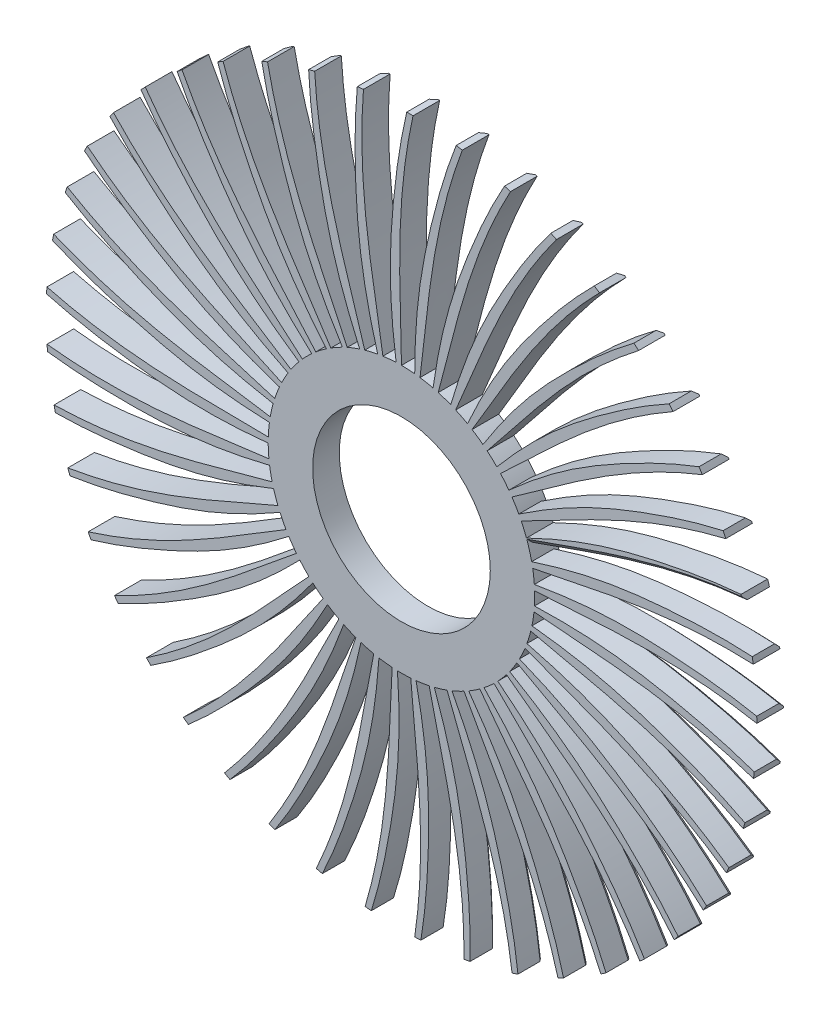
SolidWorks part; units mm, degrees
ref_plane "Front Plane" through (0, 0, 0) normal (0, 0, 1) x (1, 0, 0)
ref_plane "Top Plane" through (0, 0, 0) normal (0, 1, 0) x (1, 0, 0)
ref_plane "Right Plane" through (0, 0, 0) normal (1, 0, 0) x (0, 0, -1)
sketch "Sketch2" plane through (0, 0, 0) normal (0, 0, 1) x (1, 0, 0)
  arc A0 (13, 399.7887) -> (6, 399.955) centre (0, 0) ccw
  arc A1 (-6, 149.88) -> (-20.876, 148.5402) centre (0, 0) ccw
  arc A2 (68.5133, 394.0887) -> (61.6046, 395.2276) centre (0, 0) ccw
  arc A3 (122.6931, 380.7183) -> (116.0101, 382.8076) centre (0, 0) ccw
  arc A4 (174.4848, 359.9376) -> (168.1576, 362.9367) centre (0, 0) ccw
  arc A5 (222.8804, 332.1511) -> (217.0321, 336.0016) centre (0, 0) ccw
  arc A6 (266.9378, 297.8997) -> (261.6824, 302.5266) centre (0, 0) ccw
  arc A7 (305.7996, 257.85) -> (301.2393, 263.1633) centre (0, 0) ccw
  arc A8 (338.7094, 212.7815) -> (334.9329, 218.6778) centre (0, 0) ccw
  arc A9 (365.0265, 163.5715) -> (362.1074, 169.936) centre (0, 0) ccw
  arc A10 (384.2389, 111.1778) -> (382.2339, 117.8866) centre (0, 0) ccw
  arc A11 (395.9724, 56.6201) -> (394.9207, 63.5426) centre (0, 0) ccw
  arc A12 (399.9988, 0.9603) -> (399.9208, 7.9619) centre (0, 0) ccw
  arc A13 (396.2397, -54.7181) -> (397.1368, -47.7738) centre (0, 0) ccw
  arc A14 (384.7683, -109.3315) -> (386.6231, -102.5796) centre (0, 0) ccw
  arc A15 (365.8077, -161.8169) -> (368.5842, -155.3889) centre (0, 0) ccw
  arc A16 (339.7272, -211.1527) -> (343.3712, -205.1737) centre (0, 0) ccw
  arc A17 (307.0342, -256.3786) -> (311.4749, -250.9649) centre (0, 0) ccw
  arc A18 (268.3651, -296.6145) -> (273.516, -291.8715) centre (0, 0) ccw
  arc A19 (224.4727, -331.0771) -> (230.2335, -327.0971) centre (0, 0) ccw
  arc A20 (176.2111, -359.0956) -> (182.4698, -355.9561) centre (0, 0) ccw
  arc A21 (124.5198, -380.1247) -> (131.1545, -377.8869) centre (0, 0) ccw
  arc A22 (70.4048, -393.7552) -> (77.2864, -392.4625) centre (0, 0) ccw
  arc A23 (14.9195, -399.7217) -> (21.9141, -399.3993) centre (0, 0) ccw
  arc A24 (-40.8562, -397.908) -> (-33.8848, -398.5622) centre (0, 0) ccw
  arc A25 (-95.8367, -388.3495) -> (-89.0242, -389.9676) centre (0, 0) ccw
  arc A26 (-148.9518, -371.2322) -> (-142.4308, -373.7826) centre (0, 0) ccw
  arc A27 (-199.1677, -346.8893) -> (-193.0652, -350.3225) centre (0, 0) ccw
  arc A28 (-245.5071, -315.7946) -> (-239.9418, -320.0437) centre (0, 0) ccw
  arc A29 (-287.068, -278.5534) -> (-282.1481, -283.5356) centre (0, 0) ccw
  arc A30 (-323.0414, -235.8904) -> (-318.8628, -241.5088) centre (0, 0) ccw
  arc A31 (-352.7272, -188.636) -> (-349.3712, -194.7813) centre (0, 0) ccw
  arc A32 (-375.5475, -137.7101) -> (-373.0795, -144.2627) centre (0, 0) ccw
  arc A33 (-391.0582, -84.1038) -> (-389.5262, -90.9361) centre (0, 0) ccw
  arc A34 (-398.9575, -28.8605) -> (-398.3912, -35.8395) centre (0, 0) ccw
  arc A35 (-399.0915, 26.9445) -> (-399.502, 19.9546) centre (0, 0) ccw
  arc A36 (-391.4576, 82.2251) -> (-392.8369, 75.3603) centre (0, 0) ccw
  arc A37 (-376.2044, 135.9052) -> (-378.5257, 129.2992) centre (0, 0) ccw
  arc A38 (-353.6289, 186.9402) -> (-356.8469, 180.7215) centre (0, 0) ccw
  arc A39 (-324.1703, 234.3365) -> (-328.2226, 228.6262) centre (0, 0) ccw
  arc A40 (-288.4022, 277.1717) -> (-293.2097, 272.081) centre (0, 0) ccw
  arc A41 (-247.0206, 314.6121) -> (-252.4899, 310.24) centre (0, 0) ccw
  arc A42 (-200.8311, 345.929) -> (-206.8556, 342.3606) centre (0, 0) ccw
  arc A43 (-150.7326, 370.5127) -> (-157.1951, 367.8175) centre (0, 0) ccw
  arc A44 (-97.7003, 387.8848) -> (-104.475, 386.1152) centre (0, 0) ccw
  arc A45 (-42.7663, 397.7072) -> (-49.7214, 396.8977) centre (0, 0) ccw
  arc A46 (-26.8009, 147.5863) -> (-41.3456, 144.1893) centre (0, 0) ccw
  arc A47 (-47.0801, 142.42) -> (-61.0105, 137.0318) centre (0, 0) ccw
  arc A48 (35.5449, 145.7277) -> (20.876, 148.5402) centre (0, 0) ccw
  arc A49 (14.9176, 149.2564) -> (0, 150) centre (0, 0) ccw
  arc A50 (-66.4429, 134.4817) -> (-79.4879, 127.2072) centre (0, 0) ccw
  arc A51 (-84.5126, 123.9259) -> (-96.4181, 114.9067) centre (0, 0) ccw
  arc A52 (-100.9372, 110.958) -> (-111.4717, 100.3696) centre (0, 0) ccw
  arc A53 (55.4804, 139.3626) -> (41.3456, 144.1893) centre (0, 0) ccw
  arc A54 (74.336, 130.2849) -> (61.0105, 137.0318) centre (0, 0) ccw
  arc A55 (91.7447, 118.6714) -> (79.4879, 127.2072) centre (0, 0) ccw
  arc A56 (-115.3973, 95.8304) -> (-124.3556, 83.8789) centre (0, 0) ccw
  arc A57 (-127.6113, 78.8376) -> (-134.8191, 65.7557) centre (0, 0) ccw
  arc A58 (107.3677, 104.7481) -> (96.4181, 114.9067) centre (0, 0) ccw
  arc A59 (120.901, 88.786) -> (111.4717, 100.3696) centre (0, 0) ccw
  arc A60 (132.081, 71.0958) -> (124.3556, 83.8789) centre (0, 0) ccw
  arc A61 (-137.3414, 60.3103) -> (-142.6585, 46.3525) centre (0, 0) ccw
  arc A62 (140.6902, 52.0218) -> (134.8191, 65.7557) centre (0, 0) ccw
  arc A63 (146.561, 31.9352) -> (142.6585, 46.3525) centre (0, 0) ccw
  arc A64 (-144.3984, 40.6091) -> (-147.7212, 26.0472) centre (0, 0) ccw
  arc A65 (-148.6448, 20.1175) -> (-149.9086, 5.2349) centre (0, 0) ccw
  arc A66 (-149.998, -0.7656) -> (-149.1783, -15.6793) centre (0, 0) ccw
  arc A67 (-148.4317, -21.6339) -> (-145.5444, -36.2883) centre (0, 0) ccw
  arc A68 (-143.9763, -42.081) -> (-139.0776, -56.191) centre (0, 0) ccw
  arc A69 (-136.7186, -61.7091) -> (-129.9038, -75) centre (0, 0) ccw
  arc A70 (-126.7998, -80.1361) -> (-118.2016, -92.3492) centre (0, 0) ccw
  arc A71 (-114.413, -97.0034) -> (-104.1988, -107.901) centre (0, 0) ccw
  arc A72 (-99.7993, -111.9826) -> (-88.1678, -121.3525) centre (0, 0) ccw
  arc A73 (-83.2431, -124.7821) -> (-70.4207, -132.4421) centre (0, 0) ccw
  arc A74 (-65.0667, -135.153) -> (-51.303, -140.9539) centre (0, 0) ccw
  arc A75 (-45.6238, -142.8932) -> (-31.1868, -146.7221) centre (0, 0) ccw
  arc A76 (-25.2929, -147.8522) -> (-10.4635, -149.6346) centre (0, 0) ccw
  arc A77 (-4.4697, -149.9334) -> (10.4635, -149.6346) centre (0, 0) ccw
  arc A78 (16.4405, -149.0963) -> (31.1868, -146.7221) centre (0, 0) ccw
  arc A79 (37.0307, -145.3572) -> (51.303, -140.9539) centre (0, 0) ccw
  arc A80 (56.9001, -138.789) -> (70.4207, -132.4421) centre (0, 0) ccw
  arc A81 (75.6621, -129.5193) -> (88.1678, -121.3525) centre (0, 0) ccw
  arc A82 (108.4314, -103.6467) -> (118.2016, -92.3492) centre (0, 0) ccw
  arc A83 (121.801, -87.5472) -> (129.9038, -75) centre (0, 0) ccw
  arc A84 (132.7998, -69.7438) -> (139.0776, -56.191) centre (0, 0) ccw
  arc A85 (141.2139, -50.5829) -> (145.5444, -36.2883) centre (0, 0) ccw
  arc A86 (146.8794, -30.4375) -> (149.1783, -15.6793) centre (0, 0) ccw
  arc A87 (92.9513, -117.7287) -> (104.1988, -107.901) centre (0, 0) ccw
  arc A88 (149.6861, -9.6996) -> (149.9086, 5.2349) centre (0, 0) ccw
  arc A89 (149.5793, 11.2271) -> (147.7212, 26.0472) centre (0, 0) ccw
  spline S0 degree 3 poles (-6, 149.88) (-14.2223, 209.3858) (-13.846, 280.4019) (-1.5196, 368.6352) (6, 399.955) knots 0 0 0 0 0.599001 1 1 1 1
  spline S1 degree 3 poles (0, 150) (-1.7256, 233.452) (-7.2854, 307.5642) (13, 399.7887) knots 0 0 0 0 1 1 1 1
  spline S2 degree 3 poles (14.9176, 149.2564) (15.0569, 209.3274) (25.3131, 279.6) (49.7993, 365.2591) (61.6046, 395.2276) knots 0 0 0 0 0.599001 1 1 1 1
  spline S3 degree 3 poles (20.876, 148.5402) (30.7814, 231.4203) (35.5902, 305.585) (68.5133, 394.0887) knots 0 0 0 0 1 1 1 1
  spline S4 degree 3 poles (35.5449, 145.7277) (44.0431, 205.1947) (63.9796, 273.3561) (100.1489, 354.7737) (116.0101, 382.8076) knots 0 0 0 0 0.599001 1 1 1 1
  spline S5 degree 3 poles (41.3456, 144.1893) (62.6894, 224.8841) (77.7731, 297.6578) (122.6931, 380.7183) knots 0 0 0 0 1 1 1 1
  spline S6 degree 3 poles (55.4804, 139.3626) (72.1721, 197.0682) (101.4007, 261.7916) (148.5492, 337.3831) (168.1576, 362.9367) knots 0 0 0 0 0.599001 1 1 1 1
  spline S7 degree 3 poles (61.0105, 137.0318) (93.3771, 213.9709) (118.4421, 283.9371) (174.4848, 359.9376) knots 0 0 0 0 1 1 1 1
  spline S8 degree 3 poles (74.336, 130.2849) (98.8963, 185.1059) (136.8482, 245.1316) (194.0581, 313.4256) (217.0321, 336.0016) knots 0 0 0 0 0.599001 1 1 1 1
  spline S9 degree 3 poles (79.4879, 127.2072) (122.2473, 198.893) (156.8059, 264.6899) (222.8804, 332.1511) knots 0 0 0 0 1 1 1 1
  spline S10 degree 3 poles (91.7447, 118.6714) (123.6956, 169.5408) (169.6322, 223.7004) (235.79, 283.3677) (261.6824, 302.5266) knots 0 0 0 0 0.599001 1 1 1 1
  spline S11 degree 3 poles (96.4181, 114.9067) (148.7382, 179.9438) (192.1176, 240.2908) (266.9378, 297.8997) knots 0 0 0 0 1 1 1 1
  spline S12 degree 3 poles (107.3677, 104.7481) (146.0874, 150.6757) (199.1144, 197.9151) (272.9325, 247.7944) (301.2393, 263.1633) knots 0 0 0 0 0.599001 1 1 1 1
  spline S13 degree 3 poles (111.4717, 100.3696) (172.334, 157.4923) (223.6899, 211.2147) (305.7996, 257.85) knots 0 0 0 0 1 1 1 1
  spline S14 degree 3 poles (120.901, 88.786) (165.6356, 128.8779) (224.7211, 168.2776) (304.7626, 207.398) (334.9329, 218.6778) knots 0 0 0 0 0.599001 1 1 1 1
  spline S15 degree 3 poles (124.3556, 83.8789) (192.5756, 131.9753) (250.9084, 178.0276) (338.7094, 212.7815) knots 0 0 0 0 1 1 1 1
  spline S16 degree 3 poles (132.081, 71.0958) (181.96, 104.5716) (245.9538, 135.3648) (330.6609, 162.9649) (362.1074, 169.936) knots 0 0 0 0 0.599001 1 1 1 1
  spline S17 degree 3 poles (134.8191, 65.7557) (209.0689, 103.8896) (273.2432, 141.3753) (365.0265, 163.5715) knots 0 0 0 0 1 1 1 1
  spline S18 degree 3 poles (140.6902, 52.0218) (194.7428, 78.23) (262.3994, 99.8173) (350.1233, 115.3598) (382.2339, 117.8866) knots 0 0 0 0 0.599001 1 1 1 1
  spline S19 degree 3 poles (142.6585, 46.3525) (221.4928, 73.7818) (290.2597, 101.9714) (384.2389, 111.1778) knots 0 0 0 0 1 1 1 1
  spline S20 degree 3 poles (146.561, 31.9352) (203.7351, 50.3657) (273.7376, 62.327) (362.7709, 65.5094) (394.9207, 63.5426) knots 0 0 0 0 0.599001 1 1 1 1
  spline S21 degree 3 poles (147.7212, 26.0472) (229.6057, 42.2379) (301.6266, 60.5827) (395.9724, 56.6201) knots 0 0 0 0 1 1 1 1
  spline S22 degree 3 poles (149.5793, 11.2271) (208.7619, 21.5211) (279.7478, 23.6235) (368.3576, 14.3839) (399.9208, 7.9619) knots 0 0 0 0 0.599001 1 1 1 1
  spline S23 degree 3 poles (149.9086, 5.2349) (233.2496, 9.8719) (307.1226, 18.0148) (399.9988, 0.9603) knots 0 0 0 0 1 1 1 1
  spline S24 degree 3 poles (149.6861, -9.6996) (209.7254, -7.7423) (280.3131, -15.5398) (366.7746, -37.0216) (397.1368, -47.7738) knots 0 0 0 0 0.599001 1 1 1 1
  spline S25 degree 3 poles (149.1783, -15.6793) (232.3535, -22.6862) (306.6409, -24.9038) (396.2397, -54.7181) knots 0 0 0 0 1 1 1 1
  spline S26 degree 3 poles (146.8794, -30.4375) (206.6068, -36.8551) (275.4224, -54.4006) (358.0527, -87.7064) (386.6231, -102.5796) knots 0 0 0 0 0.599001 1 1 1 1
  spline S27 degree 3 poles (145.5444, -36.2883) (226.935, -54.8028) (300.1907, -67.3376) (384.7683, -109.3315) knots 0 0 0 0 1 1 1 1
  spline S28 degree 3 poles (141.2139, -50.5829) (199.4669, -65.2506) (265.1709, -92.2026) (342.3618, -136.6842) (368.5842, -155.3889) knots 0 0 0 0 0.599001 1 1 1 1
  spline S29 degree 3 poles (139.0776, -56.191) (217.0994, -85.8527) (287.8977, -108.4607) (365.8077, -161.8169) knots 0 0 0 0 1 1 1 1
  spline S30 degree 3 poles (132.7998, -69.7438) (188.4446, -92.376) (249.7582, -128.2099) (320.0072, -183.0015) (343.3712, -205.1737) knots 0 0 0 0 0.599001 1 1 1 1
  spline S31 degree 3 poles (129.9038, -75) (203.0382, -115.2316) (270.0011, -147.4728) (339.7272, -211.1527) knots 0 0 0 0 1 1 1 1
  spline S32 degree 3 poles (121.801, -87.5472) (173.7544, -117.7034) (229.4842, -161.7218) (291.424, -225.757) (311.4749, -250.9649) knots 0 0 0 0 0.599001 1 1 1 1
  spline S33 degree 3 poles (118.2016, -92.3492) (185.0251, -142.3676) (246.8492, -183.6145) (307.0342, -256.3786) knots 0 0 0 0 1 1 1 1
  spline S34 degree 3 poles (108.4314, -103.6467) (155.6823, -140.7399) (204.7435, -192.086) (257.1686, -264.1183) (273.516, -291.8715) knots 0 0 0 0 0.599001 1 1 1 1
  spline S35 degree 3 poles (104.1988, -107.901) (163.4107, -166.7326) (218.8927, -216.1824) (268.3651, -296.6145) knots 0 0 0 0 1 1 1 1
  spline S36 degree 3 poles (92.9513, -117.7287) (134.58, -161.037) (176.0178, -218.7114) (217.9077, -297.3389) (230.2335, -327.0971) knots 0 0 0 0 0.599001 1 1 1 1
  spline S37 degree 3 poles (88.1678, -121.3525) (138.6157, -187.8524) (186.6757, -244.5425) (224.4727, -331.0771) knots 0 0 0 0 1 1 1 1
  spline S38 degree 3 poles (75.6621, -129.5193) (110.8583, -178.1997) (143.866, -241.0798) (174.4055, -324.7721) (182.4698, -355.9561) knots 0 0 0 0 0.599001 1 1 1 1
  spline S39 degree 3 poles (70.4207, -132.4421) (111.1227, -205.3158) (150.8253, -268.1428) (176.2111, -359.0956) knots 0 0 0 0 1 1 1 1
  spline S40 degree 3 poles (56.9001, -138.789) (84.9788, -191.8939) (108.9141, -258.756) (127.5086, -345.884) (131.1545, -377.8869) knots 0 0 0 0 0.599001 1 1 1 1
  spline S41 degree 3 poles (51.303, -140.9539) (81.4668, -218.783) (112.0392, -286.5241) (124.5198, -380.1247) knots 0 0 0 0 1 1 1 1
  spline S42 degree 3 poles (37.0307, -145.3572) (57.4453, -201.8532) (71.8423, -271.3957) (78.13, -360.2636) (77.2864, -392.4625) knots 0 0 0 0 0.599001 1 1 1 1
  spline S43 degree 3 poles (31.1868, -146.7221) (50.2253, -227.9918) (71.0724, -299.3285) (70.4048, -393.7552) knots 0 0 0 0 1 1 1 1
  spline S44 degree 3 poles (16.4405, -149.0963) (28.7937, -207.8836) (33.3722, -278.753) (27.2306, -367.6312) (21.9141, -399.3993) knots 0 0 0 0 0.599001 1 1 1 1
  spline S45 degree 3 poles (10.4635, -149.6346) (18.0062, -232.763) (28.7222, -306.3068) (14.9195, -399.7217) knots 0 0 0 0 1 1 1 1
  spline S46 degree 3 poles (-4.4697, -149.9334) (-0.4183, -209.8678) (-5.7475, -280.6847) (-24.1988, -367.8432) (-33.8848, -398.5622) knots 0 0 0 0 0.599001 1 1 1 1
  spline S47 degree 3 poles (-10.4635, -149.6346) (-14.5634, -233.0037) (-14.187, -307.3232) (-40.8562, -397.908) knots 0 0 0 0 1 1 1 1
  spline S48 degree 3 poles (-25.2929, -147.8522) (-29.6222, -207.7672) (-44.7554, -277.1532) (-75.1571, -360.8955) (-89.0242, -389.9676) knots 0 0 0 0 0.599001 1 1 1 1
  spline S49 degree 3 poles (-31.1868, -146.7221) (-46.8495, -228.7093) (-56.82, -302.3579) (-95.8367, -388.3495) knots 0 0 0 0 1 1 1 1
  spline S50 degree 3 poles (-45.6238, -142.8932) (-58.2495, -201.6226) (-82.8921, -268.2272) (-124.6527, -346.9235) (-142.4308, -373.7826) knots 0 0 0 0 0.599001 1 1 1 1
  spline S51 degree 3 poles (-51.303, -140.9539) (-78.2238, -219.9634) (-98.3472, -291.5076) (-148.9518, -371.2322) knots 0 0 0 0 1 1 1 1
  spline S52 degree 3 poles (-65.0667, -135.153) (-85.7431, -191.5537) (-119.4154, -254.0805) (-171.722, -326.1989) (-193.0652, -350.3225) knots 0 0 0 0 0.599001 1 1 1 1
  spline S53 degree 3 poles (-70.4207, -132.4421) (-108.0755, -206.936) (-137.9601, -274.9834) (-199.1677, -346.8893) knots 0 0 0 0 1 1 1 1
  spline S54 degree 3 poles (-83.2431, -124.7821) (-111.5678, -177.7563) (-153.6144, -234.9884) (-215.4489, -299.1253) (-239.9418, -320.0437) knots 0 0 0 0 0.599001 1 1 1 1
  spline S55 degree 3 poles (-88.1678, -121.3525) (-135.8236, -189.881) (-174.8877, -253.1069) (-245.5071, -315.7946) knots 0 0 0 0 1 1 1 1
  spline S56 degree 3 poles (-99.7993, -111.9826) (-135.2209, -160.4992) (-184.8235, -211.3225) (-254.9824, -266.2296) (-282.1481, -283.5356) knots 0 0 0 0 0.599001 1 1 1 1
  spline S57 degree 3 poles (-104.1988, -107.901) (-160.9281, -169.13) (-208.4114, -226.304) (-287.068, -278.5534) knots 0 0 0 0 1 1 1 1
  spline S58 degree 3 poles (-114.413, -97.0034) (-156.2421, -140.1181) (-212.4352, -183.5435) (-289.5529, -228.1519) (-318.8628, -241.5088) knots 0 0 0 0 0.599001 1 1 1 1
  spline S59 degree 3 poles (-118.2016, -92.3492) (-182.9003, -145.0872) (-237.8786, -195.0964) (-323.0414, -235.8904) knots 0 0 0 0 1 1 1 1
  spline S60 degree 3 poles (-126.7998, -80.1361) (-174.2222, -117.0098) (-235.9121, -152.192) (-318.4876, -185.6336) (-349.3712, -194.7813) knots 0 0 0 0 0.599001 1 1 1 1
  spline S61 degree 3 poles (-129.9038, -75) (-201.3126, -118.2204) (-262.7158, -160.0914) (-352.7272, -188.636) knots 0 0 0 0 1 1 1 1
  spline S62 degree 3 poles (-136.7186, -61.7091) (-188.8113, -91.624) (-254.7973, -117.8782) (-341.2233, -139.5021) (-373.0795, -144.2627) knots 0 0 0 0 0.599001 1 1 1 1
  spline S63 degree 3 poles (-139.0776, -56.191) (-215.8065, -89.0526) (-282.4394, -121.9705) (-375.5475, -137.7101) knots 0 0 0 0 1 1 1 1
  spline S64 degree 3 poles (-143.9763, -42.081) (-199.7254, -64.4549) (-268.7231, -81.2701) (-357.3175, -90.6554) (-389.5262, -90.9361) knots 0 0 0 0 0.599001 1 1 1 1
  spline S65 degree 3 poles (-145.5444, -36.2883) (-226.1001, -58.1515) (-296.6658, -81.4755) (-391.0582, -84.1038) knots 0 0 0 0 1 1 1 1
  spline S66 degree 3 poles (-148.4317, -21.6339) (-206.7521, -36.0312) (-277.4185, -43.0802) (-366.4569, -40.0442) (-398.3912, -35.8395) knots 0 0 0 0 0.599001 1 1 1 1
  spline S67 degree 3 poles (-149.1783, -15.6793) (-231.9928, -26.1185) (-305.1178, -39.3947) (-398.9575, -28.8605) knots 0 0 0 0 1 1 1 1
  spline S68 degree 3 poles (-149.998, -0.7656) (-209.7546, -6.9062) (-280.7143, -4.0517) (-368.4636, 11.3465) (-399.502, 19.9546) knots 0 0 0 0 0.599001 1 1 1 1
  spline S69 degree 3 poles (-149.9086, 5.2349) (-233.3701, 6.4228) (-307.6311, 3.4529) (-399.0915, 26.9445) knots 0 0 0 0 1 1 1 1
  spline S70 degree 3 poles (-148.6448, 20.1175) (-208.6744, 22.3532) (-278.5463, 35.0556) (-363.2986, 62.5163) (-392.8369, 75.3603) knots 0 0 0 0 0.599001 1 1 1 1
  spline S71 degree 3 poles (-147.7212, 26.0472) (-230.205, 38.8391) (-304.1567, 46.2333) (-391.4576, 82.2251) knots 0 0 0 0 1 1 1 1
  spline S72 degree 3 poles (-144.3984, 40.6091) (-203.5327, 51.1775) (-270.9567, 73.4806) (-351.0625, 112.4693) (-378.5257, 129.2992) knots 0 0 0 0 0.599001 1 1 1 1
  spline S73 degree 3 poles (-142.6585, 46.3525) (-222.5593, 70.4995) (-294.7623, 88.1138) (-376.2044, 135.9052) knots 0 0 0 0 1 1 1 1
  spline S74 degree 3 poles (-137.3414, 60.3103) (-194.4294, 79.0057) (-258.0932, 110.4754) (-331.9932, 160.2332) (-356.8469, 180.7215) knots 0 0 0 0 0.599001 1 1 1 1
  spline S75 degree 3 poles (-134.8191, 65.7557) (-210.5818, 100.7877) (-279.6306, 128.2792) (-353.6289, 186.9402) knots 0 0 0 0 1 1 1 1
  spline S76 degree 3 poles (-127.6113, 78.8376) (-181.5417, 105.2962) (-240.2063, 145.3199) (-306.4622, 204.8783) (-328.2226, 228.6262) knots 0 0 0 0 0.599001 1 1 1 1
  spline S77 degree 3 poles (-124.3556, 83.8789) (-194.5055, 129.1141) (-259.0562, 165.9479) (-324.1703, 234.3365) knots 0 0 0 0 1 1 1 1
  spline S78 degree 3 poles (-115.3973, 95.8304) (-165.1206, 129.5372) (-217.644, 177.3359) (-274.9661, 245.5358) (-293.2097, 272.081) knots 0 0 0 0 0.599001 1 1 1 1
  spline S79 degree 3 poles (-111.4717, 100.3696) (-174.6433, 154.9275) (-233.4396, 200.3866) (-288.4022, 277.1717) knots 0 0 0 0 1 1 1 1
  spline S80 degree 3 poles (-100.9372, 110.958) (-145.4855, 151.2569) (-190.8455, 205.9002) (-238.1182, 281.4141) (-252.4899, 310.24) knots 0 0 0 0 0.599001 1 1 1 1
  spline S81 degree 3 poles (-96.4181, 114.9067) (-151.382, 177.7254) (-203.2794, 230.9249) (-247.0206, 314.6121) knots 0 0 0 0 1 1 1 1
  spline S82 degree 3 poles (-84.5126, 123.9259) (-123.0188, 170.0325) (-160.3325, 230.457) (-196.6356, 311.8151) (-206.8556, 342.3606) knots 0 0 0 0 0.599001 1 1 1 1
  spline S83 degree 3 poles (-79.4879, 127.2072) (-125.1741, 197.0641) (-169.1626, 256.9686) (-200.8311, 345.929) knots 0 0 0 0 1 1 1 1
  spline S84 degree 3 poles (-66.4429, 134.4817) (-98.1576, 185.4987) (-126.6987, 250.5282) (-151.3257, 336.1469) (-157.1951, 367.8175) knots 0 0 0 0 0.599001 1 1 1 1
  spline S85 degree 3 poles (-61.0105, 137.0318) (-96.5299, 212.5672) (-131.7532, 278.0107) (-150.7326, 370.5127) knots 0 0 0 0 1 1 1 1
  spline S86 degree 3 poles (-47.0801, 142.42) (-71.3859, 197.3543) (-90.5989, 265.7231) (-103.0704, 353.936) (-104.475, 386.1152) knots 0 0 0 0 0.599001 1 1 1 1
  spline S87 degree 3 poles (-41.3456, 144.1893) (-66.0069, 223.9329) (-91.7793, 293.6416) (-97.7003, 387.8848) knots 0 0 0 0 1 1 1 1
  spline S88 degree 3 poles (-26.8009, 147.5863) (-43.2248, 205.3687) (-52.7357, 275.746) (-52.8089, 364.8361) (-49.7214, 396.8977) knots 0 0 0 0 0.599001 1 1 1 1
  spline S89 degree 3 poles (-20.876, 148.5402) (-34.1991, 230.9399) (-50.0191, 303.5571) (-42.7663, 397.7072) knots 0 0 0 0 1 1 1 1
  point P230 (0, 0)
  dimension "D1" = 800
  dimension "D2" = 300
  dimension "D3" = 45
  dimension "D5" = 7
extrude "Boss-Extrude1" add sketch "Sketch2" along normal blind 30
chamfer "Chamfer1" distance 5 angle 45 45 edges
sketch "Sketch4" plane through (0, 0, 30) normal (0, 0, 1) x (1, 0, 0)
  circle A0 centre (0, 0) radius 100
  dimension "D1" = 200
extrude "Cut-Extrude4" cut sketch "Sketch4" against normal blind 30
